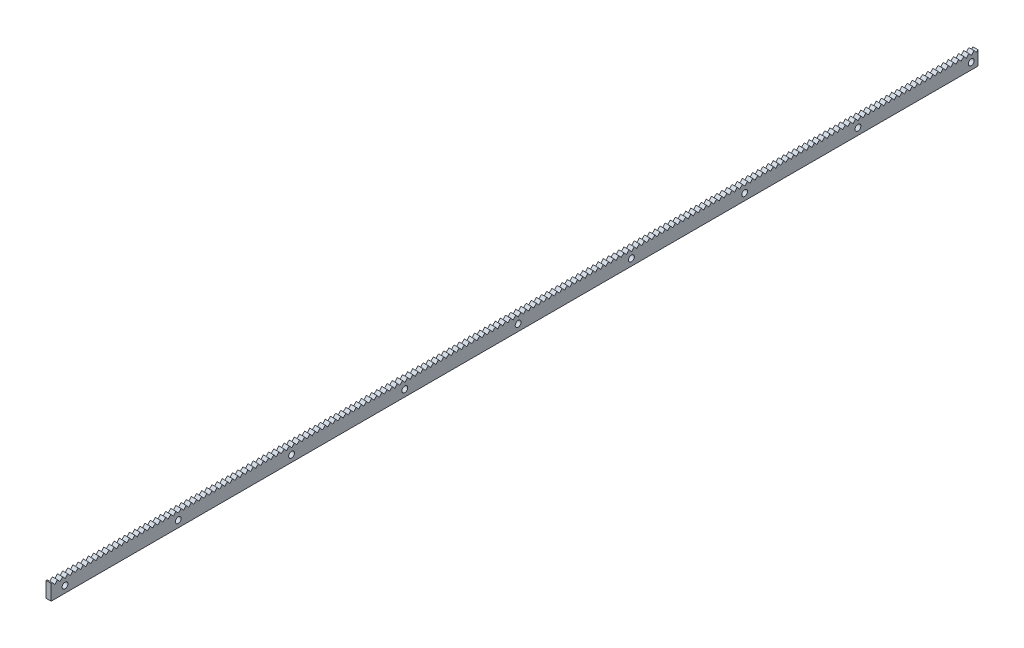
SolidWorks part; units mm, degrees
ref_plane "Front Plane" through (0, 0, 0) normal (0, 0, 1) x (1, 0, 0)
ref_plane "Top Plane" through (0, 0, 0) normal (0, 1, 0) x (1, 0, 0)
ref_plane "Right Plane" through (0, 0, 0) normal (1, 0, 0) x (0, 0, -1)
sketch "Sketch1" plane through (0, 0, 0) normal (0, 0, 1) x (1, 0, 0)
  line L1 (-18.2482, 8.4854) -> (-13.2482, 8.4854)
  line L2 (-18.2482, 8.4854) -> (-18.2482, -6.5146)
  line L3 (-18.2482, -6.5146) -> (-13.2482, -6.5146)
  line L4 (-13.2482, 8.4854) -> (-13.2482, -6.5146)
  dimension "D1" = 15
  dimension "D2" = 5
extrude "Boss-Extrude1" add sketch "Sketch1" along normal blind 900
sketch "Sketch2" plane through (-13.2482, 0, 0) normal (1, 0, 0) x (0, 0, -1)
  circle A0 centre (-886.5615, 0) radius 2.8382
extrude "Cut-Extrude1" cut sketch "Sketch2" against normal blind 900
pattern_linear "LPattern1" count 10 spacing 110 along (0, 0, -1) of "Cut-Extrude1"
sketch "Sketch3" plane through (-13.2482, 0, 0) normal (1, 0, 0) x (0, 0, -1)
  line L0 (-898.8613, 8.4854) -> (-896.3613, 5.7265)
  line L1 (-900, 8.4854) -> (0, 8.4854) construction
  line L2 (-896.3613, 5.7265) -> (-893.8613, 8.4854)
  line L3 (-898.8613, 8.4854) -> (-893.8613, 8.4854)
  dimension "D1" = 5
  dimension "D2" = 2.5
extrude "Cut-Extrude2" cut sketch "Sketch3" against normal blind 900
pattern_linear "LPattern2" count 200 spacing 5 along (0, 0, -1) of "Cut-Extrude2"
